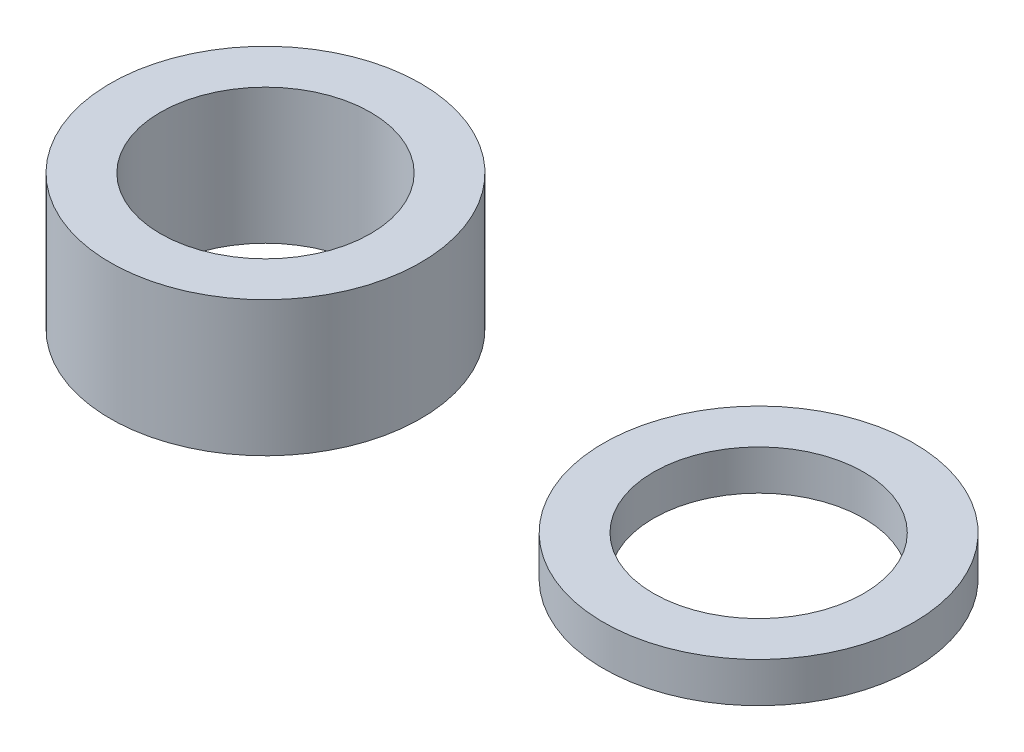
SolidWorks part; units mm, degrees
ref_plane "Front Plane" through (0, 0, 0) normal (0, 0, 1) x (1, 0, 0)
ref_plane "Top Plane" through (0, 0, 0) normal (0, 1, 0) x (1, 0, 0)
ref_plane "Right Plane" through (0, 0, 0) normal (1, 0, 0) x (0, 0, -1)
sketch "Sketch1" plane through (0, 0, 0) normal (0, 1, 0) x (1, 0, 0)
  circle A0 centre (0, 0) radius 4.2
  dimension "D1" = 8.4
extrude "Extrude-Thin1" add sketch "Sketch1" along normal blind 1.6 thin thin type one direction wall 2
sketch "Sketch2" plane through (0, 0, 0) normal (0, 1, 0) x (1, 0, 0)
  circle A0 centre (-18.4945, -1.2035) radius 4.2
  circle A2 centre (0, 0) radius 4.2 construction
extrude "Extrude-Thin2" add sketch "Sketch2" along normal blind 5.4 separate body thin thin type one direction wall 2
